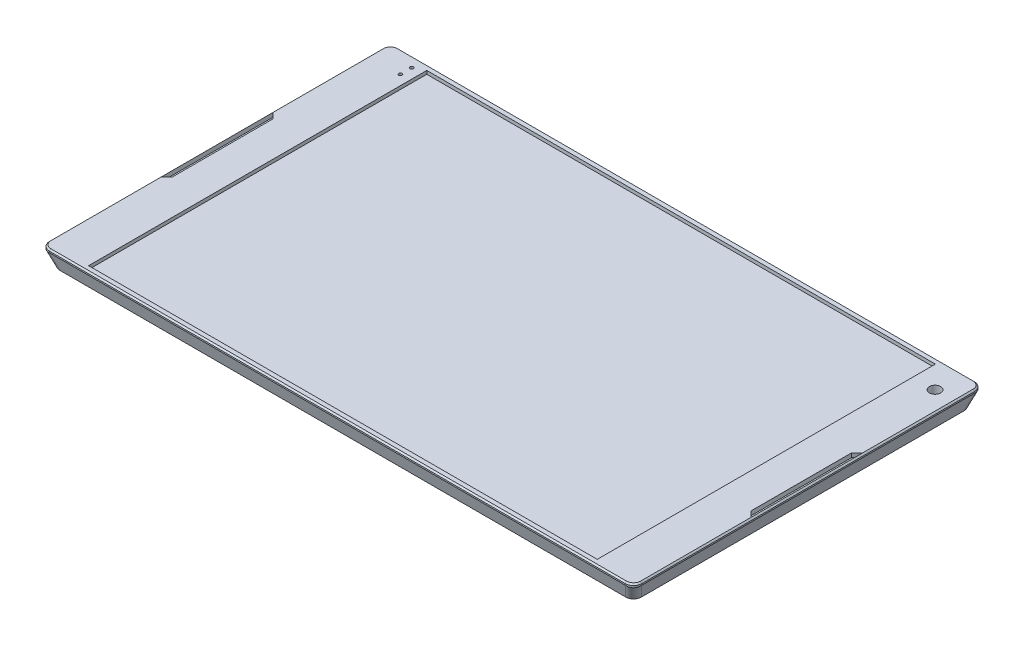
SolidWorks part; units mm, degrees
ref_plane "Front Plane" through (0, 0, 0) normal (0, 0, 1) x (1, 0, 0)
ref_plane "Top Plane" through (0, 0, 0) normal (0, 1, 0) x (1, 0, 0)
ref_plane "Right Plane" through (0, 0, 0) normal (1, 0, 0) x (0, 0, -1)
sketch "Sketch1" plane through (0, 0, 0) normal (0, 1, 0) x (1, 0, 0)
  line L1 (-132.6456, 43.3291) -> (79.3544, 43.3291)
  line L2 (-132.6456, 43.3291) -> (-132.6456, -81.6709)
  line L3 (-132.6456, -81.6709) -> (79.3544, -81.6709)
  line L4 (79.3544, 43.3291) -> (79.3544, -81.6709)
  dimension "D1" = 125
  dimension "D2" = 212
extrude "Boss-Extrude1" add sketch "Sketch1" along normal blind 6.6
sketch "Sketch2" plane through (0, 6.6, 0) normal (0, 1, 0) x (1, 0, 0)
  line L0 (79.3544, 43.3291) -> (-132.6456, 43.3291) construction
  line L1 (-117.6456, 41.3291) -> (64.3544, 41.3291)
  line L2 (-117.6456, 41.3291) -> (-117.6456, -79.6709)
  line L3 (-117.6456, -79.6709) -> (64.3544, -79.6709)
  line L4 (64.3544, 41.3291) -> (64.3544, -79.6709)
  line L5 (-132.6456, -81.6709) -> (79.3544, -81.6709) construction
  line L6 (-132.6456, 43.3291) -> (-132.6456, -81.6709) construction
  line L7 (79.3544, -81.6709) -> (79.3544, 43.3291) construction
  dimension "D1" = 2
  dimension "D2" = 2
  dimension "D3" = 15
  dimension "D4" = 15
extrude "Cut-Extrude1" cut sketch "Sketch2" against normal blind 1.2
sketch "Sketch3" plane through (0, 0, 81.6709) normal (0, 0, 1) x (1, 0, 0)
  line L0 (-132.6456, 5.6) -> (-130.6456, 0)
  line L1 (-132.6456, 6.6) -> (-132.6456, 0) construction
  line L2 (-132.6456, 0) -> (79.3544, 0) construction
  line L3 (-130.6456, 0) -> (-132.6456, 0)
  line L4 (-132.6456, 0) -> (-132.6456, 5.6)
  dimension "D1" = 1
  dimension "D2" = 2
extrude "Cut-Extrude2" cut sketch "Sketch3" against normal blind 131.2
sketch "Sketch4" plane through (0, 0, 81.6709) normal (0, 0, 1) x (1, 0, 0)
  line L0 (79.3544, 5.6) -> (77.3544, 0)
  line L1 (79.3544, 6.6) -> (79.3544, 0) construction
  line L2 (-130.6456, 0) -> (79.3544, 0) construction
  line L3 (77.3544, 0) -> (79.3544, 0)
  line L4 (79.3544, 0) -> (79.3544, 5.6)
  dimension "D1" = 1
  dimension "D2" = 2
extrude "Cut-Extrude3" cut sketch "Sketch4" against normal blind 131.2
ref_plane "Plane2" through (79.3544, 0, 0) normal (1, 0, 0) x (0, 0, -1)
sketch "Sketch5" plane through (79.3544, 0, 0) normal (1, 0, 0) x (0, 0, -1)
  line L0 (-81.6709, 5.6) -> (-79.6709, 0)
  line L1 (43.3291, 0) -> (-81.6709, 0) construction
  line L2 (-79.6709, 0) -> (-81.6709, 0)
  line L3 (-81.6709, 0) -> (-81.6709, 5.6)
  dimension "D1" = 2
extrude "Cut-Extrude4" cut sketch "Sketch5" against normal blind 221.2
sketch "Sketch6" plane through (79.3544, 0, 0) normal (1, 0, 0) x (0, 0, -1)
  line L0 (43.3291, 5.6) -> (41.3291, 0)
  line L1 (43.3291, 0) -> (-79.6709, 0) construction
  line L2 (41.3291, 0) -> (43.3291, 0)
  line L3 (43.3291, 0) -> (43.3291, 5.6)
  dimension "D1" = 2
extrude "Cut-Extrude5" cut sketch "Sketch6" against normal blind 221.2
fillet "Fillet1" radius 3 8 edges at (-132.6456, 6.1, -43.3291) (-131.6456, 2.8, -42.3291) (-132.6456, 6.1, 81.6709) (-131.6456, 2.8, 80.6709) (79.3544, 6.1, 81.6709) (78.3544, 2.8, 80.6709) (78.3544, 2.8, -42.3291) (79.3544, 6.1, -43.3291)
sketch "Sketch7" plane through (0, 0, 0) normal (0, -1, 0) x (1, 0, 0)
  line L0 (-130.6456, 76.8457) -> (-130.6456, -38.5039) construction
  line L1 (-127.8203, -41.3291) -> (74.5292, -41.3291) construction
  circle A0 centre (-125.6456, -36.3291) radius 2.5
  dimension "D1" = 5
  dimension "D2" = 5
  dimension "D3" = 5
extrude "Cut-Extrude6" cut sketch "Sketch7" against normal blind 6
sketch "Sketch8" plane through (0, 0, 0) normal (0, -1, 0) x (1, 0, 0)
  circle A0 centre (-125.6456, -36.3291) radius 3.5
  circle A1 centre (-125.6456, -36.3291) radius 2.5 construction
  dimension "D1" = 1
extrude "Cut-Extrude7" cut sketch "Sketch8" against normal blind 1
sketch "Sketch9" plane through (0, 6.6, 0) normal (0, 1, 0) x (1, 0, 0)
  line L0 (76.3544, 43.3291) -> (-129.6456, 43.3291) construction
  circle A0 centre (72.2415, 33.3291) radius 2
  dimension "D1" = 4
  dimension "D2" = 10
extrude "Cut-Extrude8" cut sketch "Sketch9" against normal blind 5
sketch "Sketch10" plane through (0, 6.6, 0) normal (0, 1, 0) x (1, 0, 0)
  line L0 (-117.6456, 41.3291) -> (-117.6456, -79.6709) construction
  circle A0 centre (-121.1456, 39.4657) radius 0.6
  circle A1 centre (-121.1573, 35.4206) radius 0.6
  dimension "D1" = 3.5
  dimension "D2" = 1.2
  dimension "D3" = 1.2
extrude "Cut-Extrude9" cut sketch "Sketch10" against normal blind 1.5
chamfer "Chamfer1" distance 0.5 angle 45 8 edges at (-26.6456, 6.6, -43.3291) (-131.7669, 6.6, -42.4504) (78.4758, 6.6, -42.4504) (-132.6456, 6.6, 19.1709) (79.3544, 6.6, 19.1709) (-131.7669, 6.6, 80.7922) (78.4758, 6.6, 80.7922) (-26.6456, 6.6, 81.6709)
sketch "Sketch11" plane through (0, 6.6, 0) normal (0, 1, 0) x (1, 0, 0)
  line L0 (-132.1456, -19.1709) -> (-132.1456, -39.1709)
  line L1 (-132.1456, 40.3291) -> (-132.1456, -78.6709) construction
  line L2 (-132.1456, -39.1709) -> (-130.1456, -37.1709)
  line L3 (-130.1456, -37.1709) -> (-130.1456, -1.1709)
  line L4 (-130.1456, -1.1709) -> (-132.1456, 0.8291)
  line L5 (-132.1456, 0.8291) -> (-132.1456, -19.1709)
  dimension "D1" = 20
  dimension "D2" = 20
  dimension "D3" = 45
  dimension "D4" = 45
  dimension "D5" = 2
extrude "Cut-Extrude10" cut sketch "Sketch11" against normal blind 1.5
sketch "Sketch12" plane through (0, 6.6, 0) normal (0, 1, 0) x (1, 0, 0)
  line L0 (78.8544, -19.1709) -> (78.8544, 0.8291)
  line L1 (78.8544, -78.6709) -> (78.8544, 40.3291) construction
  line L2 (78.8544, 0.8291) -> (76.8544, -1.1709)
  line L3 (76.8544, -1.1709) -> (76.8544, -37.1709)
  line L4 (76.8544, -37.1709) -> (78.8544, -39.1709)
  line L5 (78.8544, -39.1709) -> (78.8544, -19.1709)
  dimension "D1" = 20
  dimension "D2" = 20
  dimension "D3" = 45
  dimension "D4" = 45
  dimension "D5" = 2
extrude "Cut-Extrude11" cut sketch "Sketch12" against normal blind 1.5
